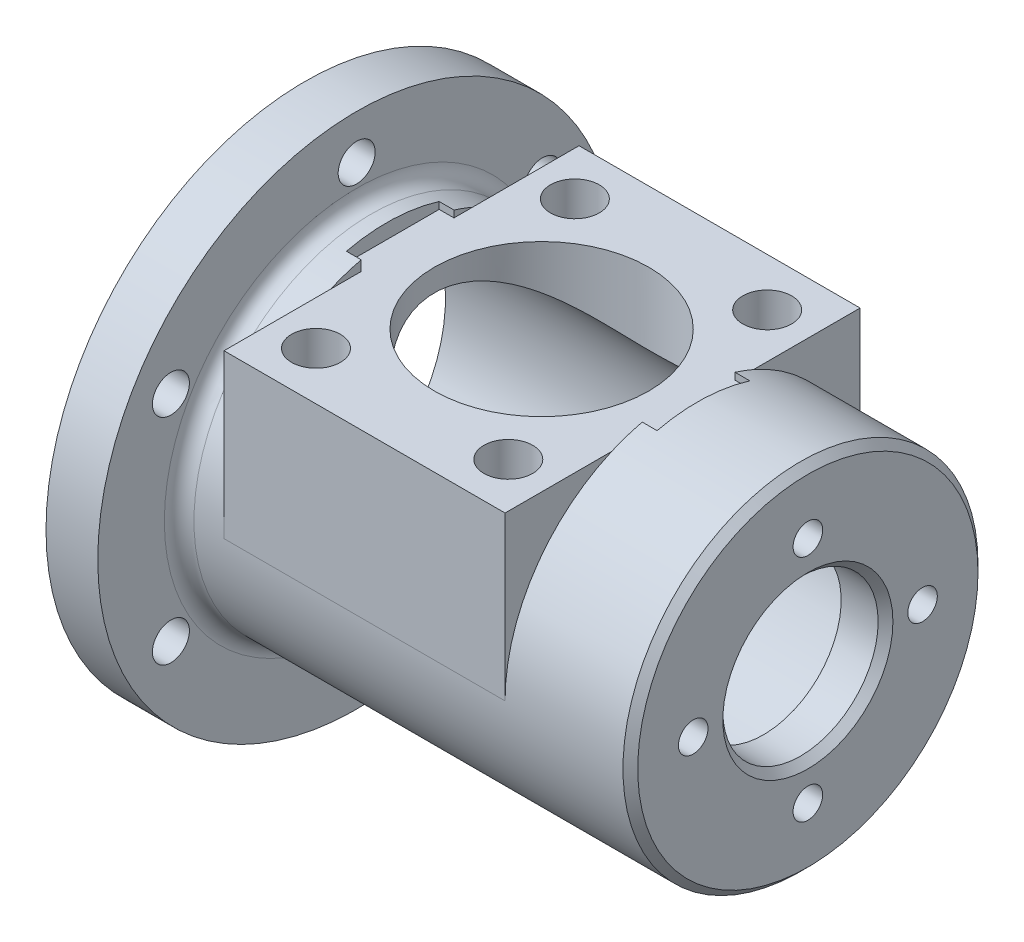
SolidWorks part; units mm, degrees
ref_plane "Piano frontale" through (0, 0, 0) normal (0, 0, 1) x (1, 0, 0)
ref_plane "Piano superiore" through (0, 0, 0) normal (0, 1, 0) x (1, 0, 0)
ref_plane "Piano destro" through (0, 0, 0) normal (1, 0, 0) x (0, 0, -1)
sketch "Schizzo1" plane through (0, 0, 0) normal (0, 1, 0) x (1, 0, 0)
  line L0 (0, -19) -> (0, -35)
  line L1 (0, -35) -> (7, -35)
  line L2 (7, -35) -> (7, -24)
  line L3 (7, -24) -> (68, -24)
  line L4 (68, -24) -> (68, -10.5)
  line L5 (68, -10.5) -> (62, -10.5)
  line L6 (62, -10.5) -> (62, -19)
  line L7 (62, -19) -> (0, -19)
  line L8 (0, 0) -> (68, 0)
  dimension "D1" = 7
  dimension "D2" = 35
  dimension "D3" = 68
  dimension "D4" = 24
  dimension "D5" = 10.5
  dimension "D6" = 19
  dimension "D7" = 62
revolve "Rivoluzione2" add sketch "Schizzo1" angle 360 about L8
sketch "Schizzo2" plane through (0, 0, 0) normal (0, 1, 0) x (1, 0, 0)
  line L0 (7, -35) -> (7, 35) construction
  circle A0 centre (32, 0) radius 14.5
  dimension "D2" = 29
  dimension "D1" = 25
sketch "Schizzo3" plane through (0, 0, 0) normal (0, 1, 0) x (1, 0, 0)
  line L0 (13.0608, 24) -> (13.0608, 7.0923)
  line L1 (68, 24) -> (7, 24) construction
  line L2 (13.0608, 7.0923) -> (11.0608, 7.0923)
  line L3 (11.0608, 7.0923) -> (11.0608, -5.4519)
  line L4 (11.0608, -5.4519) -> (13.0608, -5.4519)
  line L5 (13.0608, -5.4519) -> (13.0608, -24)
  line L6 (7, -24) -> (68, -24) construction
  line L7 (13.0608, -24) -> (51.0608, -24)
  line L8 (51.0608, -24) -> (51.0608, -5.4519)
  line L9 (51.0608, -5.4519) -> (53.0608, -5.4519)
  line L10 (53.0608, -5.4519) -> (53.0608, 7.0923)
  line L11 (53.0608, 7.0923) -> (51.0608, 7.0923)
  line L12 (51.0608, 7.0923) -> (51.0608, 24)
  line L13 (51.0608, 24) -> (13.0608, 24)
  dimension "D1" = 38
  dimension "D2" = 2
  dimension "D3" = 2
extrude "Estrusione-Estrusione1" add sketch "Schizzo3" against normal up to surface (1.0719 mm away) from offset 24 up to face at (68, 0, 24)
sketch "Schizzo4" plane through (0, 24, 0) normal (0, 1, 0) x (1, 0, 0)
  line L0 (13.0608, 24) -> (51.0608, 24)
  line L1 (51.0608, 24) -> (51.0608, 7.0923)
  line L2 (51.0608, 7.0923) -> (53.0608, 7.0923)
  line L3 (53.0608, 7.0923) -> (53.0608, -5.4519)
  line L4 (53.0608, -5.4519) -> (51.0608, -5.4519)
  line L5 (51.0608, -5.4519) -> (51.0608, -24)
  line L6 (51.0608, -24) -> (13.0608, -24)
  line L7 (13.0608, -24) -> (13.0608, -5.4519)
  line L8 (13.0608, -5.4519) -> (11.0608, -5.4519)
  line L9 (11.0608, -5.4519) -> (11.0608, 7.0923)
  line L10 (11.0608, 7.0923) -> (13.0608, 7.0923)
  line L11 (13.0608, 7.0923) -> (13.0608, 24)
extrude "Taglio-Estrusione4" cut sketch "Schizzo4" against normal blind 2
extrude "Taglio-Estrusione5" cut sketch "Schizzo2" against normal up to next from surface starting at face at (32.0608, 22, -0.4101)
sketch "Schizzo5" plane through (0, 22, 0) normal (0, 1, 0) x (1, 0, 0)
  line L1 (7, -35) -> (7, 35) construction
  point P9 (45, 17.5)
  point P10 (45, -17.5)
  point P11 (19, -17.5)
  point P16 (19, 17.5)
  dimension "D1" = 26
  dimension "D2" = 35
  dimension "D3" = 17.5
  dimension "D4" = 38
hole_wizard "Foro filettato G1/16-1" positions "Schizzo5" profile "Schizzo6" tap size "G1/16" standard "JIS"
sketch "Schizzo6" plane through (19, 22, -17.5) normal (1, 0, 0) x (0, 0, 1)
  line L0 (0, 0) -> (0, 7.9828)
  line L1 (0, 7.9828) -> (3.3, 6)
  line L2 (3.3, 6) -> (3.3, 0)
  line L5 (3.3, 0) -> (0, 0)
  line L10 (0, 7.9828) -> (-3.3, 6) construction
  line L11 (0, -6.35) -> (0, 107.95) construction
  dimension "Tap Drill Dia." = 6.6
  dimension "Tap Drill Depth" = 6
  dimension "Drill Angle" = 118
cosmetic thread "Filettatura del foro1" parameters "D1"=15.45, "D2"=7.723
cosmetic thread "Filettatura del foro2" parameters "D1"=15.45, "D2"=7.723
cosmetic thread "Filettatura del foro3" parameters "D1"=15.45, "D2"=7.723
cosmetic thread "Filettatura del foro4" parameters "D1"=15.45, "D2"=7.723
sketch "Schizzo7" plane through (68, 0, 0) normal (1, 0, 0) x (0, 0, -1)
  circle A0 centre (0, 0) radius 15.5
  circle A1 centre (0, 15.5) radius 2
  circle A2 centre (0, -15.5) radius 2
  circle A3 centre (15.5, 0) radius 2
  circle A4 centre (-15.5, 0) radius 2
  dimension "D1" = 31
  dimension "D2" = 4
  dimension "D3" = 4
  dimension "D4" = 4
  dimension "D5" = 4
extrude "Taglio-Estrusione6" cut sketch "Schizzo7" against normal up to next contours A0 A1 | A0 A1 | A0 A4 | A0 A4 | A0 A2 | A0 A2 | A0 A3 | A0 A3 region at (68, 0, -14.6284) region at (68, 0, -16.3252) region at (68, 14.6284, 0) region at (68, 16.3252, 0) region at (68, -16.3252, 0) region at (68, -14.6284, 0) region at (68, 0, 14.6284) region at (68, 0, 16.3252)
fillet "Raccordo1" radius 2 1 edges at (7, 0, 24)
chamfer "Smusso1" distance 1 angle 45 1 edges at (68, 0, 24)
fillet "Raccordo2" radius 2 1 edges at (62, 0, 19)
chamfer "Smusso2" distance 1 angle 45 1 edges at (68, 0, 10.5)
sketch "Schizzo8" plane through (7, 0, 0) normal (1, 0, 0) x (0, 0, -1)
  line L0 (-29, 0) -> (29, 0)
  line L1 (0, 29) -> (0, -29)
  line L2 (25.1147, 14.5) -> (-25.1147, -14.5)
  line L3 (-25.1147, 14.5) -> (25.1147, -14.5)
  circle A0 centre (0, 0) radius 29
  circle A1 centre (25.1147, 14.5) radius 2.5
  circle A2 centre (-25.1147, 14.5) radius 2.5
  circle A4 centre (-25.1147, -14.5) radius 2.5
  circle A5 centre (0, -29) radius 2.5
  circle A6 centre (25.1147, -14.5) radius 2.5
  circle A8 centre (0, 29) radius 2.5
  dimension "D3" = 5
  dimension "D4" = 5
  dimension "D5" = 5
  dimension "D6" = 58
  dimension "5" = 5
  dimension "D7" = 5
  dimension "D8" = 5
  dimension "D1" = 30
  dimension "D2" = 30
extrude "Taglio-Estrusione7" cut sketch "Schizzo8" against normal up to next contours A0 A8 | A0 A1 | L2 A1 A0 | A0 A1 L2 | A0 A8 L1 | L1 A8 A0 | A0 A2 | A0 A2 L3 | L3 A2 A0 | A0 A4 | A0 A4 L2 | L2 A4 A0 | A0 A5 | A0 A5 L1 | L1 A5 A0 | A0 A6 | A0 A6 L3 | L3 A6 A0 region at (7, 15.0207, 26.0166) region at (7, 13.0541, 24.7022) region at (7, -13.0541, 24.7022) region at (7, -15.0207, 26.0166) region at (7, 27.9198, 1.0459) region at (7, 27.9198, -1.0459) region at (7, -27.9198, -1.0459) region at (7, -27.9198, 1.0459) region at (7, 14.8656, -23.6563) region at (7, 13.0541, -24.7022) region at (7, -14.8656, 23.6563) region at (7, 14.8656, 23.6563) region at (7, -13.0541, -24.7022) region at (7, -14.8656, -23.6563) region at (7, 15.0207, -26.0166) region at (7, -15.0207, -26.0166) region at (7, 30.0414, 0) region at (7, -30.0414, 0)
